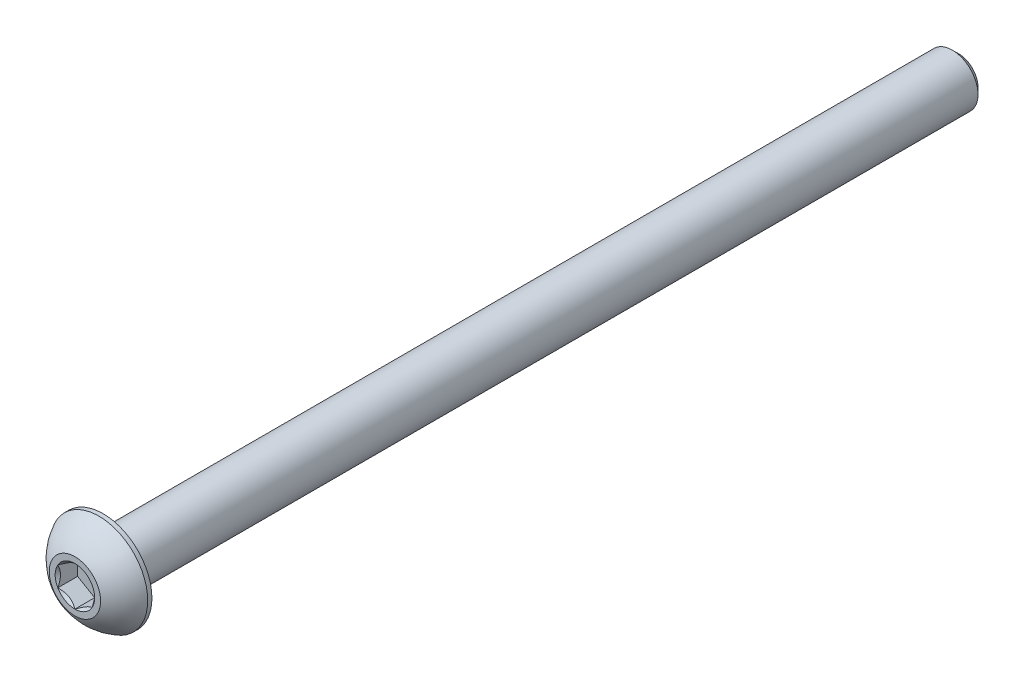
SolidWorks part; units mm, degrees
material "Chrome Stainless Steel"
ref_plane "Front" through (0, 0, 0) normal (0, 0, 1) x (1, 0, 0)
ref_plane "Top" through (0, 0, 0) normal (0, 1, 0) x (1, 0, 0)
ref_plane "Right" through (0, 0, 0) normal (1, 0, 0) x (0, 0, -1)
sketch "Sketch1" plane through (0, 0, 0) normal (1, 0, 0) x (0, 0, -1)
  line L2 (1.65, 1.5) -> (51.65, 1.5)
  line L3 (51.65, 1.5) -> (51.65, 0)
  line L4 (51.65, 0) -> (1.65, 0)
  line L6 (1.4025, 2.85) -> (1.65, 2.85) construction
  line L7 (51.65, 1.5) -> (51.65, -1.5) construction
  line L8 (0, 0) -> (1.65, 0) construction
  line L9 (1.65, 2.85) -> (1.65, -2.85) construction
  line L11 (1.65, 1.5) -> (1.65, 0)
  line L13 (0, 1) -> (0, -1) construction
  line L14 (0, 1) -> (0, 1.5) construction
  line L15 (51.6188, 1.5541) -> (51.8688, 1.1211) construction
  line L16 (51.8688, 1.1211) -> (52.1188, 1.5541) construction
  line L17 (52.1188, 1.5541) -> (51.6188, 1.5541) construction
  line L18 (51.65, 1.5) -> (52.0875, 1.5) construction
  line L19 (51.8688, 1.5541) -> (51.8688, 1.5) construction
  line L20 (51.8688, 1.5) -> (51.8688, 1.1752) construction
  line L21 (51.8688, 1.1752) -> (51.8688, 1.1211) construction
  line L22 (51.8375, 1.1752) -> (51.9, 1.1752)
  line L23 (51.6344, 1.5271) -> (52.1031, 1.5271)
  line L24 (51.9, 1.1752) -> (52.1031, 1.5271)
  line L25 (51.8375, 1.1752) -> (51.6344, 1.5271)
  line L26 (51.275, 1.5) -> (51.65, 1.125)
  arc A3 (0, 1.5) -> (1.4025, 2.85) centre (2.7948, 0) cw construction
  point P29 (51.8688, 1.5271)
  point P30 (50.4, -1.5)
  dimension "D1" = 0.2475
  dimension "Pitch" = 0.5
  dimension "D3" = 0.0625
  dimension "D2" = 0.375
  dimension "D4" = 45
  dimension "D5" = 1.25
sketch "Sketch10" plane through (0, 0, 0) normal (1, 0, 0) x (0, 0, -1)
  line L0 (51.275, 1.5) -> (51.65, 1.125) construction
  line L1 (51.275, 1.5) -> (51.65, 1.125)
  line L4 (51.65, 1.5) -> (1.65, 1.5)
  line L5 (51.65, 0) -> (51.65, 1.5)
  line L6 (1.65, 0) -> (51.65, 0)
  line L7 (1.65, 1.5) -> (1.65, 0)
  line L8 (51.275, 1.5) -> (1.65, 1.5)
  line L9 (51.65, 0) -> (51.65, 1.125)
  line L10 (1.65, 0) -> (51.65, 0)
  line L11 (1.65, 1.5) -> (1.65, 0)
  dimension "D1" = 0
revolve "Revolve3" add sketch "Sketch10" angle 360 about L8
sketch "Sketch7" plane through (0, 0, 0) normal (1, 0, 0) x (0, 0, -1)
  line L6 (1.4025, 2.85) -> (1.65, 2.85) construction
  line L8 (0, 0) -> (1.65, 0) construction
  line L11 (1.65, 2.85) -> (1.65, -2.85) construction
  line L12 (1.4025, 2.85) -> (1.65, 2.85)
  line L13 (0, 0) -> (1.65, 0)
  line L14 (0, 1) -> (0, -1) construction
  line L15 (1.65, 2.85) -> (1.65, 0)
  line L16 (0, 1.5) -> (0, 0)
  arc A2 (1.4025, 2.85) -> (0, 1.5) centre (2.7948, 0) ccw construction
  arc A3 (1.4025, 2.85) -> (0, 1.5) centre (2.7948, 0) ccw
revolve "Revolve2" add sketch "Sketch7" angle 360 mid plane about L13
sketch "Sketch5" plane through (0, 0, 0) normal (0, 0, 1) x (1, 0, 0)
  line L1 (1, -0.5774) -> (1, 0.5774)
  line L2 (1, 0.5774) -> (0, 1.1547)
  line L3 (0, 1.1547) -> (-1, 0.5774)
  line L4 (-1, 0.5774) -> (-1, -0.5774)
  line L5 (-1, -0.5774) -> (0, -1.1547)
  line L6 (0, -1.1547) -> (1, -0.5774)
  circle A0 centre (0, 0) radius 1 construction
extrude "Cut-Extrude2" cut sketch "Sketch5" against normal blind 1.155
sketch "Sketch6" plane through (0, 0, 0) normal (0, 0, 1) x (1, 0, 0)
  circle A0 centre (0, 0) radius 1.1547
extrude "Cut-Extrude3" cut sketch "Sketch6" against normal blind 1.155 draft 45
sketch "Sketch9" [suppressed] plane through (0, 0, -1.65) normal (0, 0, -1) x (-1, 0, 0)
  circle A0 centre (0, 0) radius 1.5 construction
  circle A4 centre (0, 0) radius 1.5
split "Split1" [suppressed] bodies to split 113
sketch "Sketch11" [suppressed] plane through (0, 0, -51.65) normal (0, 0, -1) x (-1, 0, 0)
  circle A0 centre (0, 0) radius 1.5 construction
  circle A1 centre (0, 0) radius 1.5
curve "Helix/Spiral1" [suppressed] pitch 0.5 height 51.65 turns 103.3
sketch "Sketch12" [suppressed] plane through (0, 0, 0) normal (1, 0, 0) x (0, 0, -1)
  line L0 (51.8375, 1.1752) -> (51.9, 1.1752) construction
  line L1 (51.9, 1.1752) -> (52.1031, 1.5271) construction
  line L2 (51.6344, 1.5271) -> (52.1031, 1.5271) construction
  line L3 (51.8375, 1.1752) -> (51.6344, 1.5271) construction
  line L4 (51.8375, 1.1752) -> (51.9, 1.1752)
  line L5 (51.9, 1.1752) -> (52.1031, 1.5271)
  line L6 (51.6344, 1.5271) -> (52.1031, 1.5271)
  line L7 (51.8375, 1.1752) -> (51.6344, 1.5271)
sweep "Cut-Sweep2" [suppressed] cut profiles "Sketch12" path "Helix/Spiral1"
extrude "Boss-Extrude1" [suppressed] add sketch "Sketch9" along normal blind 10 draft 45
equation "\"D1@Cut-Extrude2\" = \"Head Ht@Sketch1\" * .7"
equation "\"D1@Sketch1\" = \"Head Ht@Sketch1\" * .15"
equation "\"D1@Cut-Extrude3\" = \"D1@Cut-Extrude2\""
equation "\"D3@Sketch1\" = \"Pitch@Sketch1\" / 8"
equation "\"D2@Sketch1\"=\"Pitch@Sketch1\"*0.75"
equation "\"D3@Helix/Spiral1\" = \"Lg@Sketch1\" + \"Head Ht@Sketch1\""
equation "\"D4@Helix/Spiral1\"=\"pitch@sketch1\""
equation "\"D5@Sketch1\"=\"Pitch@Sketch1\"*2.5"
